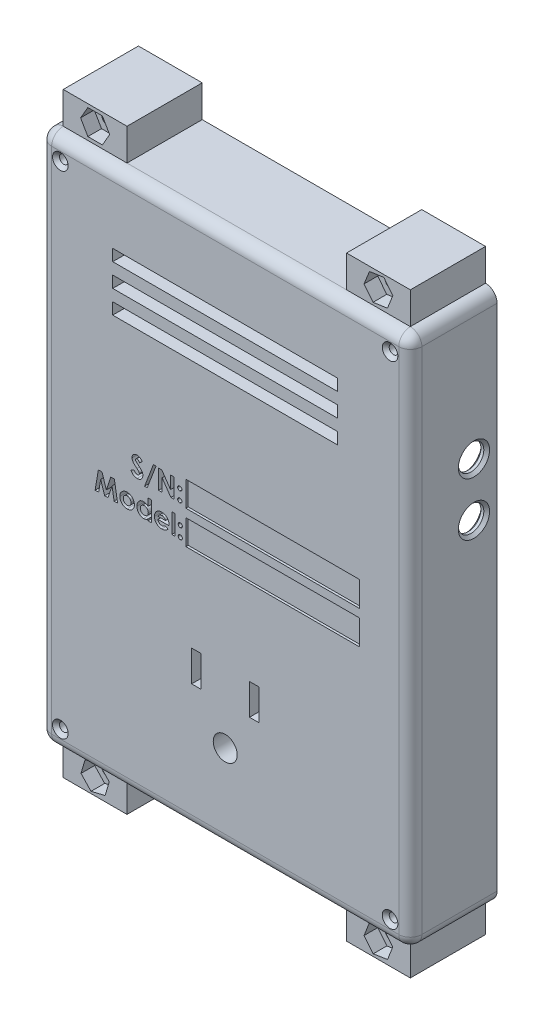
SolidWorks part; units mm, degrees
ref_plane "Front Plane" through (0, 0, 0) normal (0, 0, 1) x (1, 0, 0)
ref_plane "Top Plane" through (0, 0, 0) normal (0, 1, 0) x (1, 0, 0)
ref_plane "Right Plane" through (0, 0, 0) normal (1, 0, 0) x (0, 0, -1)
sketch "Sketch4" plane through (0, 0, 0) normal (0, 0, 1) x (1, 0, 0)
  line L1 (-36.195, 56.515) -> (36.195, 56.515)
  line L2 (-38.735, 53.975) -> (-38.735, -53.975)
  line L3 (-36.195, -56.515) -> (36.195, -56.515)
  line L4 (38.735, 53.975) -> (38.735, -53.975)
  arc A0 (-38.735, 53.975) -> (-36.195, 56.515) centre (-36.195, 53.975) ccw
  arc A1 (36.195, 56.515) -> (38.735, 53.975) centre (36.195, 53.975) ccw
  arc A2 (-36.195, -56.515) -> (-38.735, -53.975) centre (-36.195, -53.975) ccw
  arc A3 (38.735, -53.975) -> (36.195, -56.515) centre (36.195, -53.975) ccw
  dimension "D1" = 5.08
sketch "Sketch5" plane through (0, 0, 0) normal (0, 0, 1) x (1, 0, 0)
  line L0 (-40.64, -58.42) -> (40.64, -58.42)
  line L1 (-40.64, 58.42) -> (40.64, 58.42)
  line L2 (-40.64, 58.42) -> (-40.64, -58.42)
  line L3 (-40.64, -58.42) -> (40.64, -58.42) construction
  line L4 (40.64, 58.42) -> (40.64, -58.42)
  line L5 (-40.64, 58.42) -> (40.64, -58.42) construction
  line L6 (-40.64, -58.42) -> (40.64, 58.42) construction
  line L7 (-40.64, 58.42) -> (40.64, 58.42) construction
  line L9 (-40.64, 0) -> (40.64, 0) construction
  point P0 (0, 0)
sketch "Sketch8" plane through (0, 0, 0) normal (0, 0, 1) x (1, 0, 0)
  circle A0 centre (-36.195, 53.975) radius 0.9525
  circle A1 centre (-36.195, -53.975) radius 0.9525
  circle A2 centre (36.195, 53.975) radius 0.9525
  circle A3 centre (36.195, -53.975) radius 0.9525
  dimension "D1" = 1.905
extrude "Case" add sketch "Sketch5" along normal blind 12.7
extrude "Case Cut" cut sketch "Sketch4" along normal blind 7.366
ref_plane "Inside Back Plane" through (0, 0, 7.366) normal (0, 0, -1) x (-1, 0, 0)
sketch "Sketch11" plane through (0, 0, 7.366) normal (0, 0, -1) x (-1, 0, 0)
  circle A0 centre (-35.56, 48.641) radius 0.8255
  circle A1 centre (35.56, 48.641) radius 0.8255
  circle A2 centre (35.56, -48.641) radius 0.8255
  circle A3 centre (-35.56, -48.641) radius 0.8255
  dimension "D1" = 1.651
sketch "Sketch13" plane through (0, 0, 7.366) normal (0, 0, -1) x (-1, 0, 0)
  line L0 (-36.195, 51.435) -> (36.195, 51.435) construction
  line L1 (-36.195, -51.435) -> (36.195, -51.435) construction
  circle A0 centre (-35.56, 48.641) radius 2.159
  circle A1 centre (35.56, 48.641) radius 2.159
  circle A2 centre (-35.56, -48.641) radius 2.159
  circle A3 centre (35.56, -48.641) radius 2.159
  dimension "D1" = 4.318
  dimension "D2" = 2.794
  dimension "D5" = 2.794
extrude "Board Mount" add sketch "Sketch13" along normal blind 2.54
extrude "Board Mount Screw Cut" cut sketch "Sketch11" along normal blind 5.588
extrude "FacePlate Screw Cut" cut sketch "Sketch8" along normal through all
sketch "Sketch14" plane through (0, 0, 7.366) normal (0, 0, -1) x (-1, 0, 0)
  line L0 (7.366, -27.559) -> (38.735, -27.559) construction
  line L1 (-7.366, -24.1554) -> (-5.334, -24.1554)
  line L2 (-7.366, -24.1554) -> (-7.366, -30.9626)
  line L3 (-7.366, -30.9626) -> (-5.334, -30.9626)
  line L4 (-5.334, -24.1554) -> (-5.334, -30.9626)
  line L5 (5.334, -24.1554) -> (7.366, -24.1554)
  line L6 (5.334, -24.1554) -> (5.334, -30.9626)
  line L7 (5.334, -30.9626) -> (7.366, -30.9626)
  line L8 (7.366, -24.1554) -> (7.366, -30.9626)
  line L10 (-7.366, -27.559) -> (-38.735, -27.559) construction
  line L13 (-36.195, -51.435) -> (36.195, -51.435) construction
  line L14 (-6.35, -24.1554) -> (-6.35, -30.9626) construction
  line L15 (6.35, -24.1554) -> (6.35, -30.9626) construction
  circle A0 centre (0, -39.497) radius 2.6289
  dimension "D4" = 5.2578
  dimension "D6" = 11.938
  dimension "D1" = 2.032
  dimension "D2" = 6.8072
  dimension "D3" = 12.7
  dimension "D5" = 11.938
ref_plane "Left Side Plane" through (40.64, 0, 0) normal (1, 0, 0) x (0, 0, -1)
sketch "Sketch18" plane through (40.64, 0, 0) normal (1, 0, 0) x (0, 0, -1)
  line L0 (-9.017, 51.689) -> (0, 51.689) construction
  line L4 (-9.017, 50.5841) -> (0, 50.5841) construction
  line L5 (0, 42.672) -> (0, 50.5841) construction
  line L6 (-9.017, 37.1395) -> (0, 37.1395) construction
  circle A1 centre (1.27, 28.829) radius 2.794
  circle A2 centre (1.27, 17.145) radius 2.794
  dimension "D2" = 5.588
  dimension "D3" = 22.86
  dimension "D4" = 11.684
extrude "Outlet Cut" cut sketch "Sketch14" against normal through all
ref_plane "Top Back Plane" through (0, 0, 0) normal (0, 0, -1) x (-1, 0, 0)
sketch "Sketch24" plane through (0, 0, 0) normal (0, 0, 1) x (1, 0, 0)
  line L0 (-40.64, -58.42) -> (40.64, -58.42)
  line L1 (-40.64, 58.42) -> (40.64, 58.42)
  line L2 (-40.64, 58.42) -> (-40.64, -58.42)
  line L3 (-40.64, -58.42) -> (40.64, -58.42) construction
  line L4 (40.64, 58.42) -> (40.64, -58.42)
  line L5 (-40.64, 58.42) -> (40.64, -58.42) construction
  line L6 (-40.64, -58.42) -> (40.64, 58.42) construction
  line L7 (-40.64, 58.42) -> (40.64, 58.42) construction
  line L9 (-40.64, 0) -> (40.64, 0) construction
  point P0 (0, 0)
extrude "Boss-Extrude1" add sketch "Sketch24" against normal blind 6.35
sketch "Sketch26" plane through (0, 0, 0) normal (0, 0, 1) x (1, 0, 0)
  line L1 (-36.195, 56.515) -> (36.195, 56.515)
  line L2 (-38.735, 53.975) -> (-38.735, -53.975)
  line L3 (-36.195, -56.515) -> (36.195, -56.515)
  line L4 (38.735, 53.975) -> (38.735, -53.975)
  arc A0 (-38.735, 53.975) -> (-36.195, 56.515) centre (-36.195, 53.975) ccw
  arc A1 (36.195, 56.515) -> (38.735, 53.975) centre (36.195, 53.975) ccw
  arc A2 (-36.195, -56.515) -> (-38.735, -53.975) centre (-36.195, -53.975) ccw
  arc A3 (38.735, -53.975) -> (36.195, -56.515) centre (36.195, -53.975) ccw
  dimension "D1" = 5.08
extrude "Cut-Extrude1" cut sketch "Sketch26" against normal blind 6.35
fillet "Fillet11" radius 2.54 1 edges at (40.64, -58.42, 3.175) type face fillet first side face at (40.64, 0, 3.175) second side face at (0, -58.42, 3.175)
fillet "Fillet12" radius 2.54 1 edges at (40.64, 58.42, 3.175) type face fillet first side face at (0, 58.42, 3.175) second side face at (40.64, 1.27, 3.175)
fillet "Fillet13" radius 2.54 1 edges at (-40.64, 58.42, 3.175) type face fillet first side face at (-1.27, 58.42, 3.175) second side face at (-40.64, 0, 3.175)
sketch "Sketch28" plane through (0, 0, 0) normal (0, 0, -1) x (-1, 0, 0)
  circle A0 centre (-36.195, 53.975) radius 0.9525
  circle A1 centre (-36.195, -53.975) radius 0.9525
  circle A2 centre (36.195, 53.975) radius 0.9525
  circle A3 centre (36.195, -53.975) radius 0.9525
  dimension "D1" = 1.905
extrude "Cut-Extrude3" cut sketch "Sketch28" along normal through all
fillet "Fillet14" radius 2.54 1 edges at (-40.64, -58.42, 3.175) type face fillet first side face at (-40.64, -1.27, 3.175) second side face at (-1.27, -58.42, 3.175)
ref_plane "Plane1" through (0, 0, -6.35) normal (0, 0, -1) x (-1, 0, 0)
sketch "Sketch30" plane through (0, 0, -6.35) normal (0, 0, -1) x (-1, 0, 0)
  line L8 (-39.624, -57.404) -> (39.624, -57.404)
  line L10 (39.624, 57.404) -> (39.624, -57.404)
  line L11 (-39.624, 57.404) -> (39.624, 57.404)
  line L12 (-39.624, 57.404) -> (-39.624, -57.404)
  point P0 (0, 0)
extrude "Cut-Extrude4" cut sketch "Sketch30" against normal blind 2.032
fillet "Fillet15" radius 2.54 1 edges at (39.624, 57.404, -5.334) type face fillet first side face at (39.624, 0, -5.334) second side face at (0, 57.404, -5.334)
fillet "Fillet16" radius 2.54 1 edges at (-39.624, 57.404, -5.334) type face fillet first side face at (-39.624, 0, -5.334) second side face at (-1.27, 57.404, -5.334)
fillet "Fillet17" radius 2.54 1 edges at (-39.624, -57.404, -5.334) type face fillet first side face at (-39.624, -1.27, -5.334) second side face at (0, -57.404, -5.334)
fillet "Fillet18" radius 2.54 1 edges at (39.624, -57.404, -5.334) type face fillet first side face at (39.624, -1.27, -5.334) second side face at (1.27, -57.404, -5.334)
ref_plane "Plane2" through (0, 0, 12.7) normal (0, 0, 1) x (1, 0, 0)
extrude "Cut-Extrude5" cut sketch "Sketch18" against normal blind 2.54
chamfer "Chamfer6" distance 0.635 angle 45 4 edges at (40.64, 17.145, -4.064) (40.64, 28.829, -4.064) (38.735, 26.035, -1.27) (38.735, 14.351, -1.27)
fillet "Fillet19" radius 2.54 8 edges at (39.8961, -57.6761, 12.7) (0, -58.42, 12.7) (-39.8961, -57.6761, 12.7) (-40.64, 0, 12.7) (-39.8961, 57.6761, 12.7) (0, 58.42, 12.7) (39.8961, 57.6761, 12.7) (40.64, 0, 12.7)
chamfer "Chamfer7" distance 0.762 angle 45 4 edges at (37.1475, 53.975, 12.7) (-35.2425, 53.975, 12.7) (-35.2425, -53.975, 12.7) (37.1475, -53.975, 12.7)
sketch "Sketch31" plane through (0, 0, 12.7) normal (0, 0, 1) x (1, 0, 0)
  line L1 (-8.6427, 7.3091) -> (29.4287, 7.3091)
  line L2 (-8.6427, 7.3091) -> (-8.6427, 1.7965)
  line L3 (-8.6427, 1.7965) -> (29.4287, 1.7965)
  line L4 (29.4287, 7.3091) -> (29.4287, 1.7965)
  line L5 (-8.6427, 0) -> (29.4287, 0)
  line L6 (-8.6427, 0) -> (-8.6427, -5.5047)
  line L7 (-8.6427, -5.5047) -> (29.4287, -5.5047)
  line L8 (29.4287, 0) -> (29.4287, -5.5047)
extrude "Cut-Extrude6" cut sketch "Sketch31" against normal blind 0.508
sketch "Sketch32" plane through (0, 0, 12.7) normal (0, 0, 1) x (1, 0, 0)
  text T0 "S/N:" font "Century Gothic" height in points 16
  text T1 "Model:" font "Century Gothic" height in points 16
extrude "Cut-Extrude7" cut sketch "Sketch32" against normal blind 1.905
sketch "Sketch33" plane through (0, 0, 12.7) normal (0, 0, 1) x (1, 0, 0)
  line L0 (-24.6942, 41.91) -> (-38.1, 41.91) construction
  line L1 (-24.6942, 43.18) -> (24.6942, 43.18)
  line L2 (-24.6942, 43.18) -> (-24.6942, 40.64)
  line L3 (-24.6942, 40.64) -> (24.6942, 40.64)
  line L4 (24.6942, 43.18) -> (24.6942, 40.64)
  line L5 (-38.1, 55.88) -> (-38.1, -55.88) construction
  line L6 (24.6942, 41.91) -> (38.1, 41.91) construction
  line L7 (38.1, -55.88) -> (38.1, 55.88) construction
  line L8 (0, 40.64) -> (0, 38.1) construction
  line L9 (-24.6942, 38.1) -> (24.6942, 38.1)
  line L10 (-24.6942, 38.1) -> (-24.6942, 35.56)
  line L11 (-24.6942, 35.56) -> (24.6942, 35.56)
  line L12 (24.6942, 38.1) -> (24.6942, 35.56)
  line L13 (0, 35.56) -> (0, 33.02) construction
  line L14 (-24.6942, 33.02) -> (24.6942, 33.02)
  line L15 (-24.6942, 33.02) -> (-24.6942, 30.48)
  line L16 (-24.6942, 30.48) -> (24.6942, 30.48)
  line L17 (24.6942, 33.02) -> (24.6942, 30.48)
  line L18 (0, 43.18) -> (0, 55.88) construction
  line L19 (38.1, 55.88) -> (-38.1, 55.88) construction
  dimension "D1" = 2.54
  dimension "D2" = 2.54
  dimension "D3" = 2.54
  dimension "D4" = 12.7
extrude "Cut-Extrude8" cut sketch "Sketch33" against normal blind 27.94
sketch "Sketch34" plane through (0, 58.42, 0) normal (0, 1, 0) x (1, 0, 0)
  line L0 (-38.1, -10.16) -> (38.1, -10.16) construction
  line L1 (-38.1, 6.35) -> (-24.1, 6.35)
  line L2 (-38.1, 6.35) -> (-38.1, -10.16)
  line L3 (-38.1, -10.16) -> (-24.1, -10.16)
  line L4 (-24.1, 6.35) -> (-24.1, -10.16)
  line L6 (38.1, 6.35) -> (24.1, 6.35)
  line L7 (38.1, 6.35) -> (38.1, -10.16)
  line L8 (38.1, -10.16) -> (24.1, -10.16)
  line L9 (24.1, 6.35) -> (24.1, -10.16)
  dimension "D1" = 14
extrude "Boss-Extrude2" add sketch "Sketch34" along normal blind 7
sketch "Sketch35" plane through (0, -58.42, 0) normal (0, -1, 0) x (1, 0, 0)
  line L0 (38.1, 10.16) -> (-38.1, 10.16) construction
  line L1 (-38.1, -6.35) -> (-24.1, -6.35)
  line L2 (-38.1, -6.35) -> (-38.1, 10.16)
  line L3 (-38.1, 10.16) -> (-24.1, 10.16)
  line L4 (-24.1, -6.35) -> (-24.1, 10.16)
  line L5 (-38.1, -6.35) -> (38.1, -6.35) construction
  line L6 (38.1, 10.16) -> (24.1, 10.16)
  line L7 (38.1, 10.16) -> (38.1, -6.35)
  line L8 (38.1, -6.35) -> (24.1, -6.35)
  line L9 (24.1, 10.16) -> (24.1, -6.35)
  dimension "D1" = 14
extrude "Boss-Extrude3" add sketch "Sketch35" along normal blind 7
sketch "Sketch36" plane through (0, 0, 10.16) normal (0, 0, 1) x (1, 0, 0)
  circle A0 centre (-31.1, -61.92) radius 1.575
  circle A1 centre (31.1, -61.92) radius 1.575
  circle A2 centre (31.1, 61.92) radius 1.575
  circle A3 centre (-31.1, 61.92) radius 1.575
  dimension "D1" = 3.15
extrude "Cut-Extrude9" cut sketch "Sketch36" along direction (0, 0, 1) on the side against the normal up to surface (16.51 mm away) up to face at (0, 0, -6.35)
sketch "Sketch38" plane through (0, 0, 10.16) normal (0, 0, 1) x (1, 0, 0)
  line L1 (-28.0015, -61.1743) -> (-30.1965, -58.8638)
  line L2 (-30.1965, -58.8638) -> (-33.295, -59.6094)
  line L3 (-33.295, -59.6094) -> (-34.1985, -62.6657)
  line L4 (-34.1985, -62.6657) -> (-32.0035, -64.9762)
  line L5 (-32.0035, -64.9762) -> (-28.905, -64.2306)
  line L6 (-28.905, -64.2306) -> (-28.0015, -61.1743)
  line L7 (34.2485, -61.4262) -> (32.2466, -58.9464)
  line L8 (32.2466, -58.9464) -> (29.0981, -59.4403)
  line L9 (29.0981, -59.4403) -> (27.9515, -62.4138)
  line L10 (27.9515, -62.4138) -> (29.9534, -64.8936)
  line L11 (29.9534, -64.8936) -> (33.1019, -64.3997)
  line L12 (33.1019, -64.3997) -> (34.2485, -61.4262)
  line L13 (34.2544, 62.3744) -> (32.2837, 64.879)
  line L14 (32.2837, 64.879) -> (29.1293, 64.4246)
  line L15 (29.1293, 64.4246) -> (27.9456, 61.4656)
  line L16 (27.9456, 61.4656) -> (29.9163, 58.961)
  line L17 (29.9163, 58.961) -> (33.0707, 59.4154)
  line L18 (33.0707, 59.4154) -> (34.2544, 62.3744)
  line L19 (-27.913, 61.92) -> (-29.5065, 64.68)
  line L20 (-29.5065, 64.68) -> (-32.6935, 64.68)
  line L21 (-32.6935, 64.68) -> (-34.287, 61.92)
  line L22 (-34.287, 61.92) -> (-32.6935, 59.16)
  line L23 (-32.6935, 59.16) -> (-29.5065, 59.16)
  line L24 (-29.5065, 59.16) -> (-27.913, 61.92)
  circle A0 centre (-31.1, -61.92) radius 2.76 construction
  circle A1 centre (31.1, -61.92) radius 2.76 construction
  circle A2 centre (31.1, 61.92) radius 2.76 construction
  circle A3 centre (-31.1, 61.92) radius 2.76 construction
  dimension "D1" = 5.52
extrude "Cut-Extrude10" cut sketch "Sketch38" against normal blind 3
